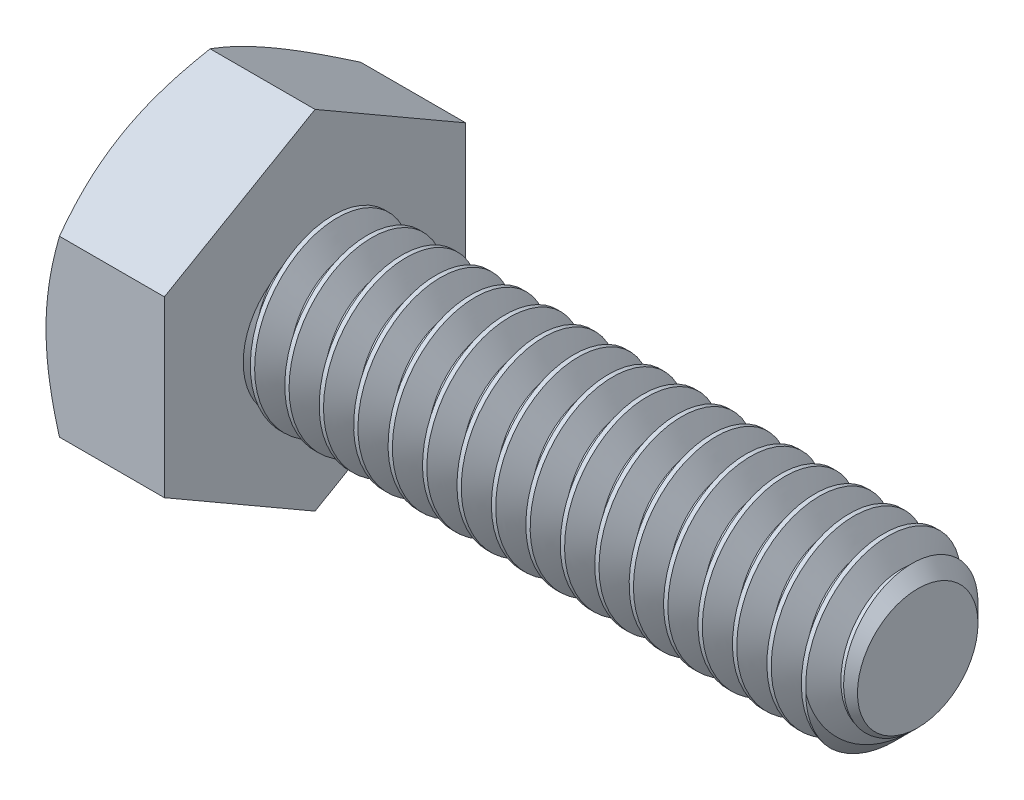
SolidWorks part; units mm, degrees
ref_plane "Front Plane" through (0, 0, 0) normal (0, 0, 1) x (1, 0, 0)
ref_plane "Top Plane" through (0, 0, 0) normal (0, 1, 0) x (1, 0, 0)
ref_plane "Right Plane" through (0, 0, 0) normal (1, 0, 0) x (0, 0, -1)
sketch "Sketch1" plane through (0, 0, 0) normal (0, 0, 1) x (1, 0, 0)
  line L0 (-13.2953, 0) -> (13.2953, 0) construction
  line L1 (13.2953, 3.175) -> (13.2953, -3.175) construction
  line L2 (-8.9297, 5.5562) -> (-8.9297, -5.5562) construction
  line L3 (-13.2953, 5.5562) -> (-13.2953, -5.5562) construction
  point P9 (-8.9297, 0)
  point P10 (8.8503, -3.175)
  dimension "D1" = 4.445
  dimension "Screw Dia" = 6.35
  dimension "Hex" = 11.1125
  dimension "Head Ht" = 4.3656
  dimension "Screw Lenght" = 22.225
ref_plane "Plane2" through (13.2953, 0, 0) normal (1, 0, 0) x (0, 0, -1)
sketch "Sketch5" plane through (13.2953, 0, 0) normal (1, 0, 0) x (0, 0, -1)
  circle A0 centre (0, 0) radius 3.175
extrude "Boss-Extrude3" add sketch "Sketch5" against normal up to vertex (22.225 mm away) up to point (-8.9297, 0, 0)
sketch "Sketch9" plane through (13.2953, 0, 0) normal (1, 0, 0) x (0, 0, -1)
  circle A1 centre (0, 0) radius 3.175
  circle A2 centre (0, 0) radius 3.175
  dimension "D1" = 0
curve "Helix/Spiral1" pitch 1.27 height 23.495 turns 18.5 parameters "Pitch"=1.27
chamfer "Chamfer1" distance 0.9525 angle 45 1 edges at (13.2953, 0, -3.175)
sketch "Sketch10" plane through (0, 0, 0) normal (0, 0, 1) x (1, 0, 0)
  line L0 (13.2953, 3.175) -> (13.7716, 2.3501)
  line L1 (13.7716, 2.3501) -> (13.9303, 2.3501)
  line L2 (13.9303, 2.3501) -> (14.4066, 3.175)
  line L3 (13.2953, 3.175) -> (14.4066, 3.175)
  line L4 (13.8509, 3.175) -> (13.8509, 2.3501) construction
  line L5 (13.5334, 2.7626) -> (14.1684, 2.7626) construction
  dimension "D1" = 60
  dimension "D2" = 0.1588
  dimension "D3" = 0.635
sweep "Cut-Sweep1" cut profiles "Sketch10" path "Helix/Spiral1"
sketch "Sketch6" plane through (-8.9297, 0, 0) normal (-1, 0, 0) x (0, 0, 1)
  line L0 (0, 5.5562) -> (0, -5.5562) construction
  line L1 (5.5562, 3.2079) -> (0, 6.4158)
  line L2 (0, 6.4158) -> (-5.5563, 3.2079)
  line L3 (-5.5563, 3.2079) -> (-5.5563, -3.2079)
  line L4 (-5.5563, -3.2079) -> (0, -6.4158)
  line L5 (0, -6.4158) -> (5.5562, -3.2079)
  line L6 (5.5562, -3.2079) -> (5.5562, 3.2079)
  circle A0 centre (0, 0) radius 5.5562 construction
extrude "Boss-Extrude4" add sketch "Sketch6" along normal up to vertex (4.3656 mm away) up to point (-13.2953, -5.5562, 0)
sketch "Sketch7" plane through (-13.2953, 0, 0) normal (-1, 0, 0) x (0, 0, 1)
  circle A0 centre (0, 0) radius 5.5562 construction
  circle A1 centre (0, 0) radius 5.5562
sketch "Sketch8" plane through (-13.2953, 0, 0) normal (-1, 0, 0) x (0, 0, 1)
  circle A0 centre (0, 0) radius 5.5562 construction
  circle A1 centre (0, 0) radius 5.5562
extrude "Cut-Extrude3" cut sketch "Sketch8" against normal through all draft 60 flip side to cut
sketch "Sketch12" plane through (-13.2953, 0, 0) normal (-1, 0, 0) x (0, 0, 1)
  line L0 (0, 4.2783) -> (0, 2.3892) construction
  line L1 (0.1667, 4.2783) -> (0.1667, 2.3892)
  line L2 (-0.1667, 4.2783) -> (-0.1667, 2.3892)
  line L3 (0, 3.175) -> (0, -3.175) construction
  arc A0 (0.1667, 4.2783) -> (-0.1667, 4.2783) centre (0, 4.2783) ccw
  arc A1 (-0.1667, 2.3892) -> (0.1667, 2.3892) centre (0, 2.3892) ccw
  circle A3 centre (0, 0) radius 2.2225 construction
  circle A4 centre (0, 0) radius 4.445 construction
  point P2 (0, 3.3337)
  dimension "D1" = 4.445
  dimension "D3" = 8.89
  dimension "D2" = 0.3334
extrude "Cut-Extrude4" cut sketch "Sketch12" against normal blind 0.254
pattern_circular "CirPattern1" count 6 over 360 about axis through (0, 0, 0) along (1, 0, 0) of "Cut-Extrude4"
equation "\"D2@Sketch10\" = \"Pitch@Helix/Spiral1\"*.125"
equation "\"D3@Sketch10\" = \"Pitch@Helix/Spiral1\"*.5"
equation "\"D3@Helix/Spiral1\" = \"Screw Lenght@Sketch1\"+\"Pitch@Helix/Spiral1\""
equation "\"D1@Chamfer1\" = \"Pitch@Helix/Spiral1\"*.75"
equation "\"D1@Sketch12\" = \"Hex@Sketch1\"*.4"
equation "\"D3@Sketch12\" = \"Hex@Sketch1\"*.8"
equation "\"D2@Sketch12\" = \"Hex@Sketch1\"*.03"
equation "\"D1@Sketch1\" = \"Pitch@Helix/Spiral1\"*3.5"
